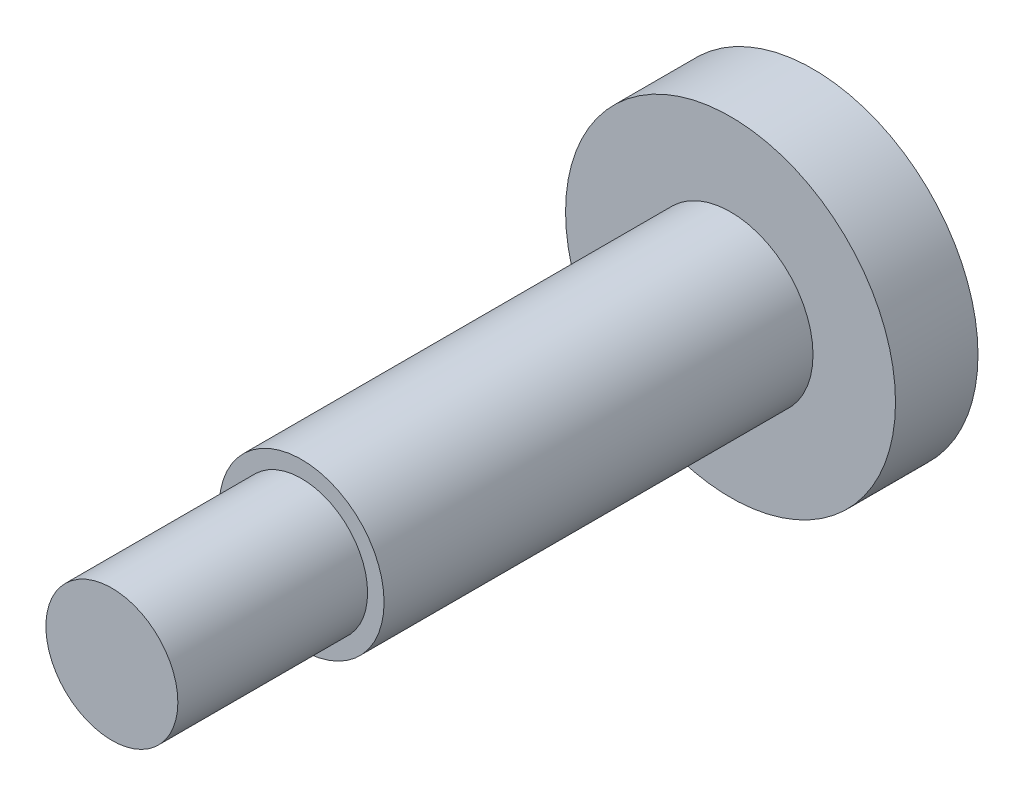
SolidWorks part; units mm, degrees
ref_plane "Front Plane" through (0, 0, 0) normal (0, 0, 1) x (1, 0, 0)
ref_plane "Top Plane" through (0, 0, 0) normal (0, 1, 0) x (1, 0, 0)
ref_plane "Right Plane" through (0, 0, 0) normal (1, 0, 0) x (0, 0, -1)
sketch "Sketch1" plane through (0, 0, 0) normal (0, 0, 1) x (1, 0, 0)
  circle A0 centre (0, 0) radius 2
extrude "Reference_Head" add sketch "Sketch1" along normal blind 1 from offset 1 offset against normal yes
sketch "Sketch2" plane through (0, 0, 0) normal (0, 0, 1) x (1, 0, 0)
  circle A0 centre (0, 0) radius 1
extrude "Reference_Shank" add sketch "Sketch2" along normal blind 7.5
sketch "Sketch3" plane through (0, 0, 7.5) normal (0, 0, 1) x (1, 0, 0)
  circle A0 centre (0, 0) radius 1.01
  circle A1 centre (0, 0) radius 0.8
extrude "M1p6_End_Thread_Envelope" cut sketch "Sketch3" against normal blind 2.3
